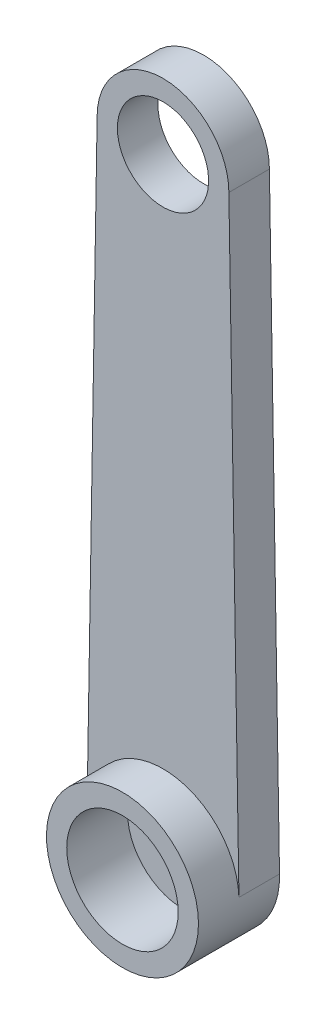
SolidWorks part; units mm, degrees
ref_plane "Plan de face" through (0, 0, 0) normal (0, 0, 1) x (1, 0, 0)
ref_plane "Plan de dessus" through (0, 0, 0) normal (0, 1, 0) x (1, 0, 0)
ref_plane "Plan de droite" through (0, 0, 0) normal (1, 0, 0) x (0, 0, -1)
sketch "Esquisse1" plane through (0, 0, 0) normal (0, 0, 1) x (1, 0, 0)
  line L0 (-2.75, 0) -> (-2.0685, 14)
  line L1 (-2.0685, 14) -> (1.9315, 14)
  line L2 (1.9315, 14) -> (2.75, 0)
  line L3 (-2.75, 0) -> (2.75, 0)
  line L4 (-2.75, 0) -> (-2.0685, -14)
  line L5 (1.9315, -14) -> (2.75, 0)
  circle A0 centre (0, 0) radius 3.75
  circle A1 centre (0, 0) radius 2.75
  circle A2 centre (-0.0685, 14) radius 2
  circle A3 centre (-0.0685, -14) radius 2
  dimension "D1" = 7.5
  dimension "D2" = 5.5
  dimension "D4" = 4
  dimension "D3" = 14
extrude "Boss.-Extru.1" add sketch "Esquisse1" along normal blind 4 contours A1 L2 A0 L0 | A1 L5 A0 L2 | A1 L4 A0 L5 | A1 L0 A0 L4 region at (-3.1161, 0, 0) region at (-2.6134, 1.4722, 0) region at (3.1077, 0, 0) region at (-0.0275, -2.8147, 0)
sketch "Sketch1" plane through (0, 0, 0) normal (0, 0, -1) x (-1, 0, 0)
  line L0 (-3.25, 30) -> (-3.75, 0)
  line L1 (3.25, 30) -> (3.75, 0)
  circle A1 centre (0, 30) radius 2.25
  circle A2 centre (0, 30) radius 3.25
  circle A3 centre (0, 0) radius 3.75 construction
  circle A4 centre (0, 0) radius 1.5
  circle M1 centre (0, 0) radius 2.75
  circle M2 centre (0, 0) radius 3.75
  dimension "D1" = 4.5
  dimension "D2" = 6.5
  dimension "D4" = 3
  dimension "D3" = 30
extrude "Boss-Extrude1" add sketch "Sketch1" against normal blind 2 contours A2 L0 L1 M2 | A2 A1 region at (0, 14.972, 0) region at (0, 33.1581, 0)
extrude "Boss-Extrude2" add sketch "Sketch1<3>" against normal blind 1 contours A4 M1 region at (2.6722, 0, 0)
sketch "Sketch1<3>" plane through (0, 0, 0) normal (0, 0, -1) x (-1, 0, 0) same geometry as "Sketch1"
